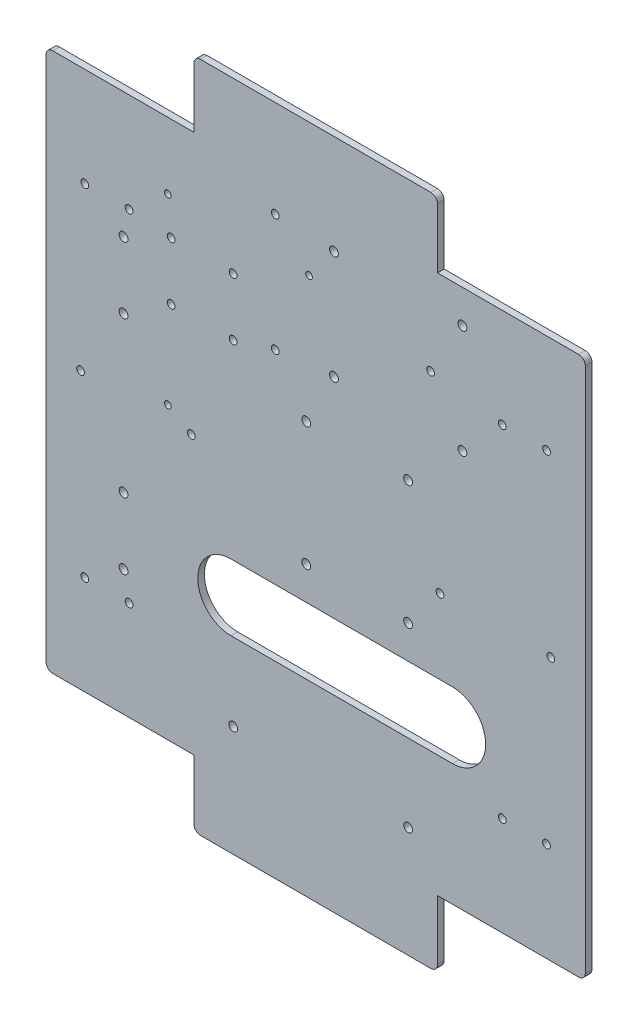
SolidWorks part; units mm, degrees
material "Alliage 1060"
ref_plane "Plan de dessus" through (0, 0, 0) normal (0, 0, 1) x (1, 0, 0)
ref_plane "Plan de droite" through (0, 0, 0) normal (0, 1, 0) x (1, 0, 0)
ref_plane "Plan de face" through (0, 0, 0) normal (1, 0, 0) x (0, 0, -1)
sketch "Esquisse1" plane through (0, 0, 0) normal (0, 0, 1) x (1, 0, 0)
  line L0 (0, 0) -> (-200, 0)
  line L1 (-200, 0) -> (-224.7487, 24.7487)
  line L2 (-224.7487, 24.7487) -> (-224.7487, 284.7487)
  line L3 (-224.7487, 284.7487) -> (-200, 309.4975)
  line L4 (-200, 309.4975) -> (0, 309.4975)
  line L5 (0, 309.4975) -> (24.7487, 284.7487)
  line L6 (24.7487, 284.7487) -> (24.7487, 24.7487)
  line L7 (24.7487, 24.7487) -> (0, 0)
  dimension "D1" = 260
  dimension "D2" = 35
  dimension "D3" = 135
  dimension "D4" = 200
extrude "Base" add sketch "Esquisse1" along normal blind 3
fillet "Congé1" radius 3 8 edges at (-200, 0, 1.5) (-224.7487, 24.7487, 1.5) (-224.7487, 284.7487, 1.5) (-200, 309.4975, 1.5) (0, 309.4975, 1.5) (24.7487, 284.7487, 1.5) (24.7487, 24.7487, 1.5) (0, 0, 1.5)
sketch "Esquisse19" plane through (0, 0, 0) normal (0, 0, -1) x (-1, 0, 0)
  line L0 (100, 309.4975) -> (100, 0) construction
  line L1 (1.2426, 309.4975) -> (198.7574, 309.4975) construction
  line L2 (198.7574, 0) -> (1.2426, 0) construction
  line L3 (-24.7487, 154.7487) -> (224.7487, 154.7487) construction
  line L4 (-24.7487, 25.9914) -> (-24.7487, 283.5061) construction
  line L5 (224.7487, 283.5061) -> (224.7487, 25.9914) construction
sketch "Esquisse25" plane through (0, 0, 0) normal (0, 0, -1) x (-1, 0, 0)
  line L0 (-24.7487, 25.9914) -> (-24.7487, 283.5061) construction
  line L1 (-21.7487, 33) -> (45, 33)
  line L2 (-24.7487, 33) -> (-24.7487, 0)
  line L3 (-24.7487, 0) -> (45, 0)
  line L4 (45, 33) -> (45, 3)
  line L5 (198.7574, 0) -> (1.2426, 0) construction
  line L6 (100, 309.4975) -> (100, 0) construction
  line L7 (100, 0) -> (100, 309.4975) construction
  line L8 (-24.7487, 154.7487) -> (224.7487, 154.7487) construction
  line L9 (224.7487, 0) -> (155, 0)
  line L10 (155, 33) -> (155, 3)
  line L11 (221.7487, 33) -> (155, 33)
  line L12 (224.7487, 33) -> (224.7487, 0)
  line L13 (224.7487, 276.4975) -> (224.7487, 309.4975)
  line L14 (221.7487, 276.4975) -> (155, 276.4975)
  line L15 (155, 276.4975) -> (155, 306.4975)
  line L16 (224.7487, 309.4975) -> (155, 309.4975)
  line L17 (-24.7487, 309.4975) -> (45, 309.4975)
  line L18 (45, 276.4975) -> (45, 306.4975)
  line L19 (-21.7487, 276.4975) -> (45, 276.4975)
  line L20 (-24.7487, 276.4975) -> (-24.7487, 309.4975)
  line L22 (45, 309.4975) -> (155, 309.4975)
  line L24 (45, 306.4975) -> (155, 306.4975)
  line L26 (45, 0) -> (155, 0)
  line L28 (45, 3) -> (155, 3)
  line L31 (-24.7487, 276.4975) -> (-24.7487, 33)
  line L33 (-21.7487, 276.4975) -> (-21.7487, 33)
  line L35 (224.7487, 276.4975) -> (224.7487, 33)
  line L37 (221.7487, 276.4975) -> (221.7487, 33)
  dimension "D1" = 55
  dimension "D2" = 33
  dimension "D3" = 3
  dimension "D4" = 3
  dimension "D5" = 3
  dimension "D6" = 3
extrude "Enlèv. mat.-Extru.1" cut sketch "Esquisse25" against normal through all
fillet "Congé2" radius 3 8 edges at (21.7487, 33, 1.5) (-45, 3, 1.5) (21.7487, 276.4975, 1.5) (-45, 306.4975, 1.5) (-155, 306.4975, 1.5) (-221.7487, 276.4975, 1.5) (-221.7487, 33, 1.5) (-155, 3, 1.5)
sketch "Esquisse33" plane through (0, 0, 3) normal (0, 0, 1) x (1, 0, 0)
  line L0 (-204.2487, 231.7487) -> (-184.2487, 231.7487) construction
  line L2 (-221.7487, 36) -> (-221.7487, 273.4975) construction
  line L3 (-221.7487, 154.7487) -> (21.7487, 154.7487) construction
  line L4 (21.7487, 273.4975) -> (21.7487, 36) construction
  line L5 (-100, 306.4975) -> (-100, 3) construction
  line L6 (-152, 306.4975) -> (-48, 306.4975) construction
  line L7 (-48, 3) -> (-152, 3) construction
  circle A0 centre (-204.2487, 231.7487) radius 1.75
  circle A1 centre (-184.2487, 231.7487) radius 1.75
  circle A2 centre (-204.2487, 77.7487) radius 1.75
  circle A3 centre (-184.2487, 77.7487) radius 1.75
  circle A4 centre (4.2487, 77.7487) radius 1.75
  circle A5 centre (-15.7513, 77.7487) radius 1.75
  circle A6 centre (4.2487, 231.7487) radius 1.75
  circle A7 centre (-15.7513, 231.7487) radius 1.75
  dimension "D3" = 3.5
  dimension "D1" = 20
  dimension "D2" = 17.5
  dimension "D4" = 77
extrude "Percage Main_De_Dieu" cut sketch "Esquisse33" against normal through all
sketch "Esquisse26" plane through (0, 0, 0) normal (0, 0, -1) x (-1, 0, 0)
  line L0 (186.7487, 189.7487) -> (186.7487, 219.7487) construction
  line L1 (221.7487, 36) -> (221.7487, 273.4975) construction
  line L2 (-24.7487, 154.7487) -> (224.7487, 154.7487) construction
  line L3 (224.7487, 154.7487) -> (-24.7487, 154.7487) construction
  line L4 (100, 309.4975) -> (100, 0) construction
  circle A0 centre (186.7487, 189.7487) radius 2
  circle A1 centre (186.7487, 219.7487) radius 2
  circle A2 centre (186.7487, 89.7487) radius 2
  circle A3 centre (186.7487, 119.7487) radius 2
  point P8 (186.7487, 204.7487)
  dimension "D1" = 4
  dimension "D2" = 30
  dimension "D3" = 35
  dimension "D4" = 50
extrude "Percage Buck Converter" cut sketch "Esquisse26" against normal through all
sketch "Esquisse27" plane through (0, 0, 0) normal (0, 0, -1) x (-1, 0, 0)
  line L0 (137.2513, 53) -> (58.2513, 53) construction
  line L1 (-21.7487, 273.4975) -> (-21.7487, 36) construction
  line L2 (-18.7487, 33) -> (45, 33) construction
  circle A0 centre (137.2513, 53) radius 2
  circle A1 centre (58.2513, 53) radius 2
  dimension "D2" = 4
  dimension "D1" = 79
  dimension "D3" = 80
  dimension "D4" = 20
extrude "Percage Teensy Moteur" cut sketch "Esquisse27" against normal through all
sketch "Esquisse28" plane through (0, 0, 0) normal (0, 0, -1) x (-1, 0, 0)
  line L0 (166.7487, 164.0225) -> (166.7487, 246.4975) construction
  line L1 (166.7487, 246.4975) -> (102.9987, 246.4975) construction
  line L2 (224.7487, 154.7487) -> (-24.7487, 154.7487) construction
  line L3 (221.7487, 36) -> (221.7487, 273.4975) construction
  line L4 (218.7487, 276.4975) -> (155, 276.4975) construction
  circle A0 centre (166.7487, 246.4975) radius 1.5
  circle A1 centre (102.9987, 246.4975) radius 1.5
  circle A2 centre (166.7487, 164.0225) radius 1.5
  dimension "D1" = 3
  dimension "D2" = 63.75
  dimension "D3" = 82.475
  dimension "D4" = 55
  dimension "D5" = 30
extrude "Percage Carte Alim" cut sketch "Esquisse28" against normal through all
sketch "Esquisse29" plane through (0, 0, 0) normal (0, 0, -1) x (-1, 0, 0)
  line L0 (221.7487, 36) -> (221.7487, 273.4975) construction
  line L1 (91.7487, 212.4975) -> (33.7487, 212.4975) construction
  line L2 (91.7487, 212.4975) -> (91.7487, 261.4975) construction
  line L3 (91.7487, 261.4975) -> (33.7487, 261.4975) construction
  line L4 (33.7487, 212.4975) -> (33.7487, 261.4975) construction
  line L5 (218.7487, 276.4975) -> (155, 276.4975) construction
  circle A0 centre (91.7487, 212.4975) radius 2
  circle A1 centre (33.7487, 212.4975) radius 2
  circle A2 centre (33.7487, 261.4975) radius 2
  circle A3 centre (91.7487, 261.4975) radius 2
  dimension "D3" = 4
  dimension "D1" = 49
  dimension "D2" = 58
  dimension "D4" = 130
  dimension "D5" = 15
extrude "Percage Rasp" cut sketch "Esquisse29" against normal through all
sketch "Esquisse32" plane through (0, 0, 3) normal (0, 0, 1) x (1, 0, 0)
  line L0 (-118.2513, 262.8275) -> (-118.2513, 209.8275) construction
  line L1 (-48.1113, 236.4975) -> (-118.2513, 236.4975) construction
  line L2 (-45, 276.4975) -> (18.7487, 276.4975) construction
  line L3 (21.7487, 273.4975) -> (21.7487, 36) construction
  circle A0 centre (-118.2513, 262.8275) radius 1.75
  circle A1 centre (-118.2513, 209.8275) radius 1.75
  circle A2 centre (-48.1113, 236.4975) radius 1.75
  dimension "D1" = 3.5
  dimension "D2" = 53
  dimension "D3" = 70.14
  dimension "D4" = 26.33
  dimension "D5" = 40
  dimension "D6" = 140
extrude "Percage Teensy Actionneurs" cut sketch "Esquisse32" against normal through all
sketch "Esquisse30" plane through (0, 0, 0) normal (0, 0, -1) x (-1, 0, 0)
  line L0 (-21.7487, 273.4975) -> (-21.7487, 36) construction
  line L1 (104.2513, 133) -> (58.2513, 133) construction
  line L2 (104.2513, 133) -> (104.2513, 188.8) construction
  line L3 (104.2513, 188.8) -> (58.2513, 188.8) construction
  line L4 (58.2513, 133) -> (58.2513, 188.8) construction
  line L5 (-18.7487, 33) -> (45, 33) construction
  circle A0 centre (104.2513, 133) radius 2
  circle A1 centre (58.2513, 133) radius 2
  circle A2 centre (58.2513, 188.8) radius 2
  circle A3 centre (104.2513, 188.8) radius 2
  dimension "D3" = 4
  dimension "D1" = 55.8
  dimension "D2" = 46
  dimension "D4" = 80
  dimension "D5" = 100
extrude "Percage Alim Actionneurs" cut sketch "Esquisse30" against normal through all
sketch "Esquisse31" plane through (0, 0, 0) normal (0, 0, -1) x (-1, 0, 0)
  line L0 (138.2513, 103) -> (38.2513, 103) construction
  line L1 (138.2513, 88) -> (38.2513, 88)
  line L2 (138.2513, 118) -> (38.2513, 118)
  line L3 (-18.7487, 33) -> (45, 33) construction
  line L4 (-21.7487, 273.4975) -> (-21.7487, 36) construction
  arc A0 (138.2513, 88) -> (138.2513, 118) centre (138.2513, 103) ccw
  arc A1 (38.2513, 118) -> (38.2513, 88) centre (38.2513, 103) ccw
  point P2 (88.2513, 103)
  dimension "D2" = 15
  dimension "D1" = 100
  dimension "D3" = 70
  dimension "D4" = 60
extrude "Enlèv. mat.-Extru.7" cut sketch "Esquisse31" against normal through all
sketch "Esquisse34" plane through (0, 0, 0) normal (0, 0, -1) x (-1, 0, 0)
  line L0 (221.7487, 154.7487) -> (-21.7487, 154.7487) construction
  line L1 (221.7487, 36) -> (221.7487, 273.4975) construction
  line L2 (-21.7487, 273.4975) -> (-21.7487, 36) construction
  line L3 (206.1487, 157.7487) -> (156.1487, 157.7487) construction
  line L5 (100, 306.4975) -> (100, 3) construction
  line L6 (152, 306.4975) -> (48, 306.4975) construction
  line L7 (48, 3) -> (152, 3) construction
  circle A2 centre (156.1487, 157.7487) radius 1.75
  circle A3 centre (206.1487, 157.7487) radius 1.75
  circle A6 centre (-6.1487, 151.7487) radius 1.75
  circle A7 centre (43.8513, 151.7487) radius 1.75
  point P12 (181.1487, 157.7487)
  dimension "D2" = 3.5
  dimension "D1" = 3
  dimension "D3" = 50
  dimension "D4" = 40.6
extrude "Enlèv. mat.-Extru.10" cut sketch "Esquisse34" against normal through all
sketch "Esquisse35" plane through (0, 0, 3) normal (0, 0, 1) x (1, 0, 0)
  line L1 (-165.2758, 230.0724) -> (-137.2758, 230.0724) construction
  line L2 (-165.2758, 230.0724) -> (-165.2758, 204.0724) construction
  line L3 (-165.2758, 204.0724) -> (-137.2758, 204.0724) construction
  line L4 (-137.2758, 230.0724) -> (-137.2758, 204.0724) construction
  circle A0 centre (-165.2758, 230.0724) radius 1.75
  circle A1 centre (-137.2758, 230.0724) radius 1.75
  circle A2 centre (-137.2758, 204.0724) radius 1.75
  circle A3 centre (-165.2758, 204.0724) radius 1.75
  dimension "D3" = 3.5
  dimension "D1" = 28
  dimension "D2" = 26
extrude "Enlèv. mat.-Extru.11" cut sketch "Esquisse35" against normal through all
